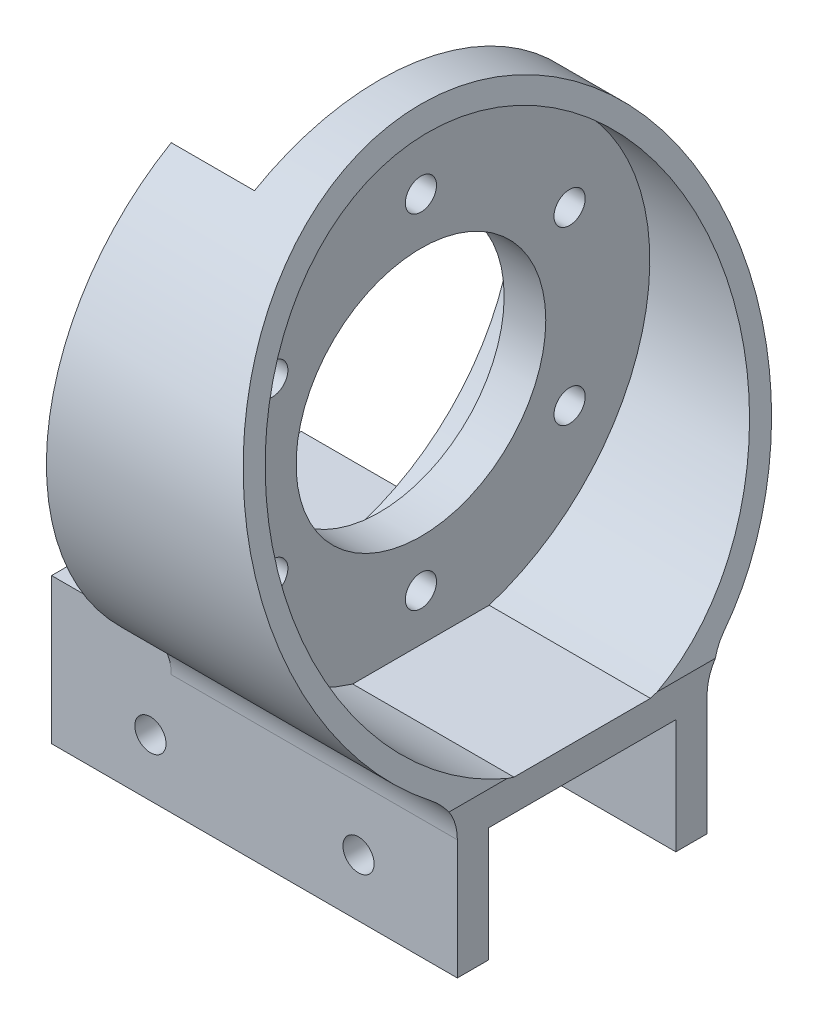
SolidWorks part; units mm, degrees
material "6061 合金"
ref_plane "前视基准面" through (0, 0, 0) normal (0, 0, 1) x (1, 0, 0)
ref_plane "上视基准面" through (0, 0, 0) normal (0, 1, 0) x (1, 0, 0)
ref_plane "右视基准面" through (0, 0, 0) normal (1, 0, 0) x (0, 0, -1)
sketch "草图1" plane through (0, 0, 0) normal (0, 0, 1) x (1, 0, 0)
  line L1 (-17, -14.5) -> (17, -14.5)
  line L2 (-17, -14.5) -> (-17, 14.5)
  line L3 (-17, 14.5) -> (17, 14.5)
  line L4 (17, -14.5) -> (17, 14.5)
  line L5 (-17, -14.5) -> (17, 14.5) construction
  line L6 (-17, 14.5) -> (17, -14.5) construction
  point P0 (0, 0)
  dimension "D1" = 34
  dimension "D2" = 29
extrude "凸台-拉伸1" add sketch "草图1" along normal blind 20
sketch "草图2" plane through (0, 0, 20) normal (0, 0, 1) x (1, 0, 0)
  line L9 (-12, 9.5) -> (-12, 16.0588)
  line L10 (-12, 16.0588) -> (12, 16.0588)
  line L11 (12, 16.0588) -> (12, 9.5)
  line L13 (12, -9.5) -> (12, 9.5)
  line L14 (12, 9.5) -> (-12, 9.5)
  line L15 (-12, 9.5) -> (-12, -9.5)
  line L16 (-12, -9.5) -> (12, -9.5)
  line L17 (12, -9.5) -> (12, 9.5)
  line L19 (-12, 9.5) -> (-12, -9.5)
  line L20 (-12, -9.5) -> (12, -9.5)
  dimension "D1" = 5
extrude "切除-拉伸1" cut sketch "草图2" against normal through all
sketch "草图3" plane through (17, 0, 0) normal (1, 0, 0) x (0, 0, -1)
  line L0 (-20, 14.5) -> (0, 14.5) construction
  circle A0 centre (-10, 2.5) radius 2.75
  dimension "D1" = 5.5
  dimension "D2" = 12
extrude "切除-拉伸2" cut sketch "草图3" against normal through all
sketch "草图4" plane through (17, 0, 0) normal (1, 0, 0) x (0, 0, -1)
  line L0 (-10, 2.5) -> (-10, 14.5) construction
  line L1 (-20, 14.5) -> (0, 14.5) construction
  line L2 (-10, 2.5) -> (-15.8839, 12.6912) construction
  circle A0 centre (-10, 2.5) radius 7 construction
  circle A1 centre (-13.5, 8.5622) radius 1.65
  circle A2 centre (-3.9378, 6) radius 1.65
  circle A3 centre (-6.5, -3.5622) radius 1.65
  circle A4 centre (-16.0622, -1) radius 1.65
  point P18 (-10, 2.5)
  dimension "D1" = 30
  dimension "D2" = 4
extrude "切除-拉伸3" cut sketch "草图4" against normal blind 20
sketch "草图5" plane through (17, 0, 0) normal (1, 0, 0) x (0, 0, -1)
  line L0 (-25, -9.5) -> (5, -9.5)
  line L1 (-20, -14.5) -> (0, -14.5) construction
  line L2 (-20, -14.5) -> (-20, 14.5) construction
  line L3 (0, -14.5) -> (0, 14.5) construction
  line L4 (-25, -9.5) -> (-25, -34.5)
  line L5 (-25, -34.5) -> (-20, -34.5)
  line L6 (-20, -34.5) -> (-20, -14.5)
  line L7 (-20, -14.5) -> (0, -14.5)
  line L8 (0, -14.5) -> (0, -34.5)
  line L9 (0, -34.5) -> (5, -34.5)
  line L10 (5, -34.5) -> (5, -9.5)
  dimension "D1" = 5
  dimension "D2" = 5
  dimension "D3" = 5
extrude "凸台-拉伸2" add sketch "草图5" along normal blind 15 and the other way blind 40
sketch "草图6" plane through (32, 0, 0) normal (1, 0, 0) x (0, 0, -1)
  line L6 (-20.7, -34.5) -> (0.7, -34.5)
  line L9 (0.7, -13.8) -> (0.7, -34.5)
  line L10 (-20.7, -13.8) -> (0.7, -13.8)
  line L11 (-20.7, -34.5) -> (-20.7, -13.8)
  line L12 (0.7, -13.8) -> (0.7, -34.5)
  line L13 (-20.7, -13.8) -> (0.7, -13.8)
  line L14 (-20.7, -34.5) -> (-20.7, -13.8)
  dimension "D1" = 0.7
extrude "切除-拉伸4" cut sketch "草图6" against normal through all
sketch "草图8" plane through (17, 0, 0) normal (1, 0, 0) x (0, 0, -1)
  line L0 (-20, 14.5) -> (-20, -9.5)
  line L1 (-20, 14.5) -> (-25, -9.5)
  line L2 (-25, -9.5) -> (-20, -9.5)
  line L3 (0, 14.5) -> (0, -9.5)
  line L4 (0, -9.5) -> (5, -9.5)
  line L5 (5, -9.5) -> (0, 14.5)
extrude "凸台-拉伸3" add sketch "草图8" against normal up to surface (5 mm away) up to face at (12, -1, 14.4122)
sketch "草图9" plane through (-17, 0, 0) normal (-1, 0, 0) x (0, 0, 1)
  line L0 (0, 14.5) -> (-5, -9.5)
  line L1 (-5, -9.5) -> (0, -9.5)
  line L2 (0, -9.5) -> (0, 14.5)
  line L3 (20, 14.5) -> (20, -9.5)
  line L4 (20, -9.5) -> (25, -9.5)
  line L5 (25, -9.5) -> (20, 14.5)
extrude "凸台-拉伸4" add sketch "草图9" against normal up to surface (5 mm away) up to face at (-12, 2.5, 12.75)
fillet "圆角1" radius 10 4 edges at (14.5, 14.5, 0) (14.5, 14.5, 20) (-14.5, 14.5, 20) (-14.5, 14.5, 0)
sketch "草图11" plane through (32, 0, 0) normal (1, 0, 0) x (0, 0, -1)
  line L0 (-10, -13.8) -> (-10, -34.5) construction
  line L1 (0.7, -13.8) -> (-20.7, -13.8) construction
  circle A0 centre (-10, -24.15) radius 12
  dimension "D1" = 24
extrude "切除-拉伸6" cut sketch "草图11" against normal blind 56
sketch "草图12" plane through (32, 0, 0) normal (1, 0, 0) x (0, 0, -1)
  line L0 (-10, -24.15) -> (-10, -12.15) construction
  line L1 (-10, -24.15) -> (8.0772, -13.7131)
  line L2 (-10, -24.15) -> (-28.0772, -13.7131)
  line L3 (-28.0772, -13.7131) -> (-28.0772, -37.2815)
  line L4 (-28.0772, -37.2815) -> (9.633, -37.2815)
  line L5 (9.633, -37.2815) -> (8.0772, -13.7131)
  arc A0 (-3.9273, -13.8) -> (-16.0727, -13.8) centre (-10, -24.15) ccw construction
  dimension "D1" = 60
extrude "切除-拉伸7" cut sketch "草图12" against normal blind 56
sketch "草图13" plane through (32, 0, 0) normal (1, 0, 0) x (0, 0, -1)
  line L0 (5, -15.4897) -> (0.7, -17.9724) construction
  line L1 (-20.7, -17.9724) -> (-25, -15.4897) construction
  line L2 (5, -15.4897) -> (0.3923, -18.15)
  line L3 (-20.3923, -18.15) -> (-25, -15.4897)
  line L4 (5, -9.5) -> (-25, -9.5) construction
  line L5 (-0.76, -9.5) -> (-19.24, -9.5)
  arc A0 (0.3923, -18.15) -> (-20.3923, -18.15) centre (-10, -24.15) ccw
  arc A1 (5, -15.4897) -> (-0.76, -9.5) centre (-10, -24.15) ccw
  arc A2 (-19.24, -9.5) -> (-25, -15.4897) centre (-10, -24.15) ccw
extrude "凸台-拉伸5" add sketch "草图13" against normal up to surface (55 mm away) up to face at (-23, -13.9474, 10)
sketch "草图14" plane through (32, 0, 0) normal (1, 0, 0) x (0, 0, -1)
  line L0 (-10, -12.15) -> (-10, -6.8295) construction
  line L1 (1.5911, -21.0442) -> (6.7303, -19.6671)
  line L2 (-21.5911, -21.0442) -> (-26.7303, -19.6671)
  line L3 (5, -9.5) -> (-25, -9.5) construction
  line L4 (-0.76, -9.5) -> (-19.24, -9.5)
  arc A0 (1.5911, -21.0442) -> (-21.5911, -21.0442) centre (-10, -24.15) ccw
  arc A1 (6.7303, -19.6671) -> (-0.76, -9.5) centre (-10, -24.15) ccw
  arc A2 (-19.24, -9.5) -> (-26.7303, -19.6671) centre (-10, -24.15) ccw
  dimension "D1" = 75
extrude "凸台-拉伸6" add sketch "草图14" against normal up to surface (55 mm away) contours L4 A2 L2 A0 L1 A1 up to face at (-23, -13.3799, 10)
sketch "草图15" plane through (32, 0, 0) normal (1, 0, 0) x (0, 0, -1)
  line L0 (-10, -12.15) -> (-10, -24.65) construction
  arc A0 (1.5911, -21.0442) -> (-21.5911, -21.0442) centre (-10, -24.15) ccw construction
  circle A1 centre (-10, -24.65) radius 12.5
  dimension "D1" = 12.5
extrude "切除-拉伸8" cut sketch "草图15" against normal blind 180
sketch "草图17" plane through (32, 0, 0) normal (1, 0, 0) x (0, 0, -1)
  line L0 (-10, -24.65) -> (-10, -12.15) construction
  line L1 (-10, -24.65) -> (5.8905, -15.4756) construction
  line L2 (-10, -24.65) -> (-25.8905, -15.4756) construction
  line L3 (-20.8253, -18.4) -> (-14.9708, -8.2597) construction
  line L4 (0.8253, -18.4) -> (-5.6497, -7.1849) construction
  arc A0 (1.9401, -20.9507) -> (-21.9401, -20.9507) centre (-10, -24.65) ccw construction
  dimension "D1" = 60
sketch "草图18" plane through (32, 0, 0) normal (1, 0, 0) x (0, 0, -1)
  line L0 (-10, -24.65) -> (-10, -24.5) construction
  circle A1 centre (-10, -24.5) radius 12.5
  dimension "D1" = 0.15
  dimension "D2" = 25
extrude "切除-拉伸9" cut sketch "草图18" against normal blind 58
sketch "草图21" plane through (-23, 0, 0) normal (-1, 0, 0) x (0, 0, 1)
  line L1 (-17.6613, 18.996) -> (42.1159, 18.996)
  line L2 (-17.6613, 18.996) -> (-17.6613, -31.8849)
  line L3 (-17.6613, -31.8849) -> (42.1159, -31.8849)
  line L4 (42.1159, 18.996) -> (42.1159, -31.8849)
extrude "切除-拉伸10" cut sketch "草图21" against normal blind 16
sketch "草图22" plane through (17, 0, 0) normal (1, 0, 0) x (0, 0, -1)
  line L1 (-25, -9.5) -> (5, -9.5)
  line L2 (-25, -9.5) -> (-25, 14.5)
  line L3 (-25, 14.5) -> (5, 14.5)
  line L4 (5, -9.5) -> (5, 14.5)
  circle A0 centre (-6.5, -3.5622) radius 1.65 construction
  circle A1 centre (-3.9378, 6) radius 1.65 construction
  circle A2 centre (-13.5, 8.5622) radius 1.65 construction
  circle A3 centre (-10, 2.5) radius 2.75 construction
  circle A4 centre (-16.0622, -1) radius 1.65 construction
  circle A5 centre (-6.5, -3.5622) radius 1.65
  circle A6 centre (-3.9378, 6) radius 1.65
  circle A7 centre (-13.5, 8.5622) radius 1.65
  circle A8 centre (-10, 2.5) radius 2.75
  circle A9 centre (-16.0622, -1) radius 1.65
  dimension "D1" = 24
  dimension "D2" = 30
extrude "凸台-拉伸7" add sketch "草图22" against normal up to surface (5 mm away) up to face at (12, -1, 14.4122)
sketch "草图23" plane through (17, 0, 0) normal (1, 0, 0) x (0, 0, -1)
  line L4 (-25, 14.5) -> (-25, -9.5)
  line L5 (-25, -9.5) -> (5, -9.5)
  line L6 (5, -9.5) -> (5, 14.5)
  line L7 (5, 14.5) -> (-25, 14.5)
  line L8 (-25, 14.5) -> (-25, -9.5)
  line L9 (-25, -9.5) -> (5, -9.5)
  line L10 (5, -9.5) -> (5, 14.5)
  line L11 (5, 14.5) -> (-25, 14.5)
  dimension "D1" = 0
extrude "切除-拉伸11" cut sketch "草图23" against normal blind 1
sketch "草图24" plane through (16, 0, 0) normal (1, 0, 0) x (0, 0, -1)
  line L1 (-25, 14.5) -> (-23, 14.5)
  line L2 (-25, 14.5) -> (-25, -9.5)
  line L3 (-25, -9.5) -> (-23, -9.5)
  line L4 (-23, 14.5) -> (-23, -9.5)
  line L5 (-25, -9.5) -> (5, -9.5) construction
  line L7 (5, 14.5) -> (3, 14.5)
  line L8 (5, 14.5) -> (5, -9.5)
  line L9 (5, -9.5) -> (3, -9.5)
  line L10 (3, 14.5) -> (3, -9.5)
  circle A0 centre (-10, 2.5) radius 10.5 construction
  dimension "D1" = 21
  dimension "D2" = 24
  dimension "D3" = 2
  dimension "D4" = 24
  dimension "D5" = 2
extrude "凸台-拉伸8" add sketch "草图24" along normal up to surface (16 mm away) up to face at (32, -15.2675, 10)
sketch "草图25" plane through (0, 0, -3) normal (0, 0, 1) x (1, 0, 0)
  line L0 (16, 14.5) -> (32, -9.5)
  line L1 (32, -9.5) -> (32, 14.5)
  line L2 (32, 14.5) -> (16, 14.5)
extrude "切除-拉伸12" cut sketch "草图25" against normal mid plane 62
sketch "草图26" plane through (32, 0, 0) normal (1, 0, 0) x (0, 0, -1)
  line L0 (5, -15.4897) -> (5, -25.9673)
  line L1 (5, -25.9673) -> (8.7839, -25.4832)
  line L2 (8.7839, -25.4832) -> (7.5054, -15.4897)
  line L3 (7.5054, -15.4897) -> (5, -15.4897)
  line L4 (-25, -15.4897) -> (-25, -25.9673)
  line L5 (-25, -25.9673) -> (-32.0692, -23.4308)
  line L6 (-32.0692, -23.4308) -> (-32.0692, -17.5217)
  line L7 (-32.0692, -17.5217) -> (-25, -15.4897)
extrude "切除-拉伸13" cut sketch "草图26" against normal blind 62
sketch "草图28" plane through (32, 0, 0) normal (1, 0, 0) x (0, 0, -1)
  line L0 (1.9822, -20.9394) -> (5, -20.9394)
  line L1 (5, -20.9394) -> (5, -20.1308)
  line L2 (5, -20.1308) -> (1.9822, -20.9394)
  line L3 (-21.9822, -20.9394) -> (-25, -20.9394)
  line L4 (-25, -20.9394) -> (-25, -20.1308)
  line M1 (1.9822, -20.9394) -> (5, -20.1308)
  line M7 (-25, -20.1308) -> (-21.9822, -20.9394)
extrude "凸台-拉伸9" add sketch "草图28" along direction (-1, 0, 0) on the side against the normal up to surface (39 mm away) contours L0 L1 M1 | L4 L3 M7 region at (32, -20.6698, -3.9941) region at (32, -20.6698, 23.9941) up to face at (-7, -15.3668, 10)
sketch "草图30" plane through (12, 0, 0) normal (-1, 0, 0) x (0, 0, 1)
  arc A2 (-0.4941, 2.1468) -> (-2.4952, 9.1423) centre (-15.4856, 1.6423) ccw
  arc A3 (-0.4941, 2.1468) -> (15.5529, 11.4115) centre (10, 2.5) ccw
  arc A5 (10.4952, 16.6423) -> (15.5529, 11.4115) centre (23.4856, 24.1423) ccw
sketch "草图32" plane through (-7, 0, 0) normal (-1, 0, 0) x (0, 0, 1)
  line L0 (10, -12) -> (10, -24.5) construction
  line L1 (10, -24.5) -> (25.0466, -15.8128) construction
  line L2 (20.8253, -18.25) -> (16.0889, -10.0462) construction
  arc A0 (21.9822, -20.9394) -> (-1.9822, -20.9394) centre (10, -24.5) ccw construction
  dimension "D1" = 60
ref_plane "基准面1" through (0, 4.4551, 7.7165) normal (0, 0.5, 0.866) x (0, 0.866, -0.5)
ref_plane "基准面2" through (0, 0, 10) normal (0, 0, -1) x (-1, 0, 0)
fillet "圆角3" radius 4 2 edges at (24, -9.5, 23) (24, -9.5, -3)
sketch "草图35" plane through (12, 0, 0) normal (-1, 0, 0) x (0, 0, 1)
  line L3 (25, 13.4808) -> (22.4952, 9.1423)
  line L4 (25, -9.5) -> (25, 14.5) construction
  line L5 (-5, -9.5) -> (25, -9.5) construction
  line L6 (-5, 14.5) -> (-5, -9.5) construction
  line L7 (-5, 14.5) -> (25, 14.5) construction
  line L8 (25, -9.5) -> (25, 13.4808)
  line L9 (-5, -9.5) -> (25, -9.5)
  line L10 (-5, 14.5) -> (-5, -9.5)
  line L11 (-5, 14.5) -> (8.0047, 14.5)
  arc A3 (4.4471, 11.4115) -> (8.0047, 14.5) centre (-3.4856, 24.1423) ccw
  arc A4 (22.4952, 9.1423) -> (20.4941, 2.1468) centre (35.4856, 1.6423) ccw
  arc A5 (4.4471, 11.4115) -> (20.4941, 2.1468) centre (10, 2.5) ccw
extrude "凸台-拉伸10" add sketch "草图35" along normal blind 8
sketch "草图36" plane through (12, 0, 0) normal (-1, 0, 0) x (0, 0, 1)
  line L1 (25, -9.5) -> (-5, -9.5)
  line L2 (25, -9.5) -> (25, 14.5)
  line L3 (25, 14.5) -> (-5, 14.5)
  line L4 (-5, -9.5) -> (-5, 14.5)
extrude "切除-拉伸15" cut sketch "草图36" along normal blind 13
sketch "草图37" plane through (16, 0, 0) normal (1, 0, 0) x (0, 0, -1)
  circle A0 centre (-10, 2.5) radius 11.5
  dimension "D1" = 23
extrude "切除-拉伸16" cut sketch "草图37" against normal blind 13
sketch "草图38" plane through (12, 0, 0) normal (-1, 0, 0) x (0, 0, 1)
  line L4 (-5, -9.5) -> (25, -9.5)
  line L5 (25, -9.5) -> (25, 14.5)
  line L6 (25, 14.5) -> (-5, 14.5)
  line L7 (-5, 14.5) -> (-5, -9.5)
  line L8 (-5, -9.5) -> (25, -9.5)
  line L9 (25, -9.5) -> (25, 14.5)
  line L10 (25, 14.5) -> (-5, 14.5)
  line L11 (-5, 14.5) -> (-5, -9.5)
  dimension "D1" = 0
extrude "切除-拉伸17" cut sketch "草图38" against normal blind 28
ref_plane "基准面3" through (12.5, 0, 0) normal (1, 0, 0) x (0, 0, -1)
sketch "草图39" plane through (12.5, 0, 0) normal (1, 0, 0) x (0, 0, -1)
  line L0 (-10, -9.5) -> (-10, 11.5) construction
  line L1 (5, -9.5) -> (-25, -9.5) construction
  circle A0 centre (-10, 11.5) radius 12
  circle A1 centre (-10, 11.5) radius 21
  circle A2 centre (-10, 11.5) radius 16.5 construction
  circle A3 centre (-10, 28) radius 1.5
  circle A4 centre (4.2894, 19.75) radius 1.5
  circle A5 centre (4.2894, 3.25) radius 1.5
  circle A6 centre (-10, -5) radius 1.5
  circle A7 centre (-24.2894, 3.25) radius 1.5
  circle A8 centre (-24.2894, 19.75) radius 1.5
  point P25 (-10, 11.5)
  dimension "D2" = 24
  dimension "D3" = 42
  dimension "D4" = 33
  dimension "D5" = 3
  dimension "D1" = 21
  dimension "D6" = 6
extrude "凸台-拉伸11" add sketch "草图39" along normal blind 4 separate body
sketch "草图42" plane through (16.5, 0, 0) normal (1, 0, 0) x (0, 0, -1)
  line L0 (5, -9.5) -> (5, -3.1969)
  line L1 (5, -3.1969) -> (-10, -7.4384)
  line L2 (-10, -7.4384) -> (-25, -3.1969)
  line L3 (-25, -3.1969) -> (-25, -9.5)
  line L4 (5, -9.5) -> (-25, -9.5) construction
  line L5 (-25, -9.5) -> (5, -9.5)
  circle A0 centre (-10, 11.5) radius 21 construction
extrude "凸台-拉伸14" add sketch "草图42" against normal blind 4
fillet "圆角5" radius 10 2 edges at (14.5, -3.1969, -5) (14.5, -3.1969, 25)
sketch "草图43" plane through (12.5, 0, 0) normal (-1, 0, 0) x (0, 0, 1)
  line L3 (25, -9.5) -> (-5, -9.5) construction
  line L4 (21.619, -9.5) -> (-1.619, -9.5)
  line L5 (25, -6.8303) -> (25, -9.5) construction
  line L6 (-5, -9.5) -> (-5, -6.8303) construction
  line L7 (25, -7.235) -> (25, -9.5)
  line L8 (-5, -9.5) -> (-5, -7.235)
  line L9 (25, -9.5) -> (-5, -9.5)
  line L10 (-2, 11.5) -> (-14, 11.5)
  line L11 (16, 21.8923) -> (22, 32.2846)
  line L12 (10, 11.5) -> (10, 32.5)
  arc A0 (26.9355, -0.9173) -> (-6.9355, -0.9173) centre (10, 11.5) ccw construction
  arc A3 (-14, 11.5) -> (-5, -7.235) centre (10, 11.5) ccw
  arc A4 (-11, 11.5) -> (20.5, 29.6865) centre (10, 11.5) ccw
  arc A5 (25, -7.235) -> (22, 32.2846) centre (10, 11.5) ccw
  circle A6 centre (10, 11.5) radius 12 construction
  arc A7 (-2, 11.5) -> (16, 21.8923) centre (10, 11.5) ccw
  line M1 (25, -9.5) -> (25, -6.8303)
  arc M2 (25, -6.8303) -> (26.9355, -0.9173) centre (35, -6.8303) cw
  arc M3 (26.9355, -0.9173) -> (-6.9355, -0.9173) centre (10, 11.5) ccw
  arc M4 (-6.9355, -0.9173) -> (-5, -6.8303) centre (-15, -6.8303) cw
  line M5 (-5, -6.8303) -> (-5, -9.5)
  line M6 (-5, -9.5) -> (25, -9.5)
  dimension "D1" = 48
  dimension "D2" = 30
extrude "凸台-拉伸15" add sketch "草图43" against normal blind 4 contours A4 M4 M5 M6 | A4 L9 M6 M1 M2 | A5 M1 M3 M2 | A3 M5 M4 M3 region at (12.5, -7.4887, 21.5485) region at (12.5, -7.4887, -1.5485) region at (12.5, 2.6841, -10.0948) region at (12.5, 15.9074, 30.9592)
extrude "凸台-拉伸16" add sketch "草图43<4>" along normal blind 8 contours A4 L9 M6 M1 M2 | A4 M4 M5 M6 | A3 M5 M4 M3 | A5 M1 M3 M2 region at (12.5, -7.4887, 21.5485) region at (12.5, -7.4887, -1.5485) region at (12.5, 2.6841, -10.0948) region at (12.5, 15.9074, 30.9592)
sketch "草图43<4>" plane through (12.5, 0, 0) normal (-1, 0, 0) x (0, 0, 1) same geometry as "草图43"
sketch "草图45" plane through (12.5, 0, 0) normal (-1, 0, 0) x (0, 0, 1)
  line L0 (-11, 11.5) -> (-14, 11.5) construction
  line L1 (20.5, 29.6865) -> (22, 32.2846) construction
  line L2 (-11, 11.5) -> (-14, 11.5)
  line L3 (20.5, 29.6865) -> (22, 32.2846)
  arc A0 (22, 32.2846) -> (-14, 11.5) centre (10, 11.5) ccw
  arc A1 (20.5, 29.6865) -> (-11, 11.5) centre (10, 11.5) ccw
extrude "凸台-拉伸18" add sketch "草图45" against normal up to surface (4 mm away) up to face at (16.5, 7.5452, 7.5685)
sketch "草图49" plane through (-7, 0, 0) normal (-1, 0, 0) x (0, 0, 1)
  line L0 (10, -9.5) -> (10, -12.5) construction
  line L1 (25, -9.5) -> (-5, -9.5) construction
  line L2 (10, -12.5) -> (22.5, -12.5) construction
  line L4 (22.5, -12.5) -> (-2.5, -12.5)
  line L5 (22.5, -12.5) -> (22.5, -37.5)
  line L6 (22.5, -37.5) -> (-2.5, -37.5)
  line L7 (-2.5, -12.5) -> (-2.5, -37.5)
  dimension "D1" = 3
  dimension "D2" = 12.5
  dimension "D3" = 25
extrude "切除-拉伸20" cut sketch "草图49" against normal blind 45
sketch "草图50" plane through (-7, 0, 0) normal (-1, 0, 0) x (0, 0, 1)
  line L0 (6.5, -12.5) -> (13.5, -12.5)
  arc A0 (13.5, -12.5) -> (6.5, -12.5) centre (10, -24.5) ccw construction
  arc A1 (13.5, -12.5) -> (6.5, -12.5) centre (10, -24.5) ccw
extrude "凸台-拉伸20" add sketch "草图50" against normal up to surface (39 mm away) up to face at (32, -15.2258, 10)
sketch "草图51" plane through (0, -20.9394, 0) normal (0, -1, 0) x (1, 0, 0)
  line L4 (-7, 25) -> (-7, 22.5)
  line L5 (-7, 22.5) -> (32, 22.5)
  line L6 (32, 22.5) -> (32, 25)
  line L7 (32, 25) -> (-7, 25)
  line L8 (-7, 25) -> (-7, 22.5)
  line L9 (-7, 22.5) -> (32, 22.5)
  line L10 (32, 22.5) -> (32, 25)
  line L11 (32, 25) -> (-7, 25)
  line L12 (32, -2.5) -> (-7, -2.5)
  line L13 (-7, -2.5) -> (-7, -5)
  line L14 (-7, -5) -> (32, -5)
  line L15 (32, -5) -> (32, -2.5)
  line L16 (32, -2.5) -> (-7, -2.5)
  line L17 (-7, -2.5) -> (-7, -5)
  line L18 (-7, -5) -> (32, -5)
  line L19 (32, -5) -> (32, -2.5)
  dimension "D1" = 0
  dimension "D2" = 0
extrude "凸台-拉伸21" add sketch "草图51" along normal blind 11.56
sketch "草图52" plane through (0, 0, 25) normal (0, 0, 1) x (1, 0, 0)
  line L0 (-7, -32.4994) -> (-7, -22.4994) construction
  line L1 (-7, -9.5) -> (-7, -32.4994) construction
  line L2 (-7, -22.4994) -> (32, -22.4994) construction
  line L3 (32, -9.5) -> (32, -32.4994) construction
  line L5 (-2.5, -28.4994) -> (27.5, -28.4994) construction
  line L6 (-2.5, -28.4994) -> (-2.5, -16.4994) construction
  line L7 (-2.5, -16.4994) -> (27.5, -16.4994) construction
  line L8 (27.5, -28.4994) -> (27.5, -16.4994) construction
  line L9 (-2.5, -28.4994) -> (27.5, -16.4994) construction
  line L10 (-2.5, -16.4994) -> (27.5, -28.4994) construction
  circle A0 centre (-2.5, -16.4994) radius 1.5
  circle A1 centre (-2.5, -28.4994) radius 1.5
  circle A2 centre (27.5, -16.4994) radius 1.5
  circle A3 centre (27.5, -28.4994) radius 1.5
  point P8 (12.5, -22.4994)
  dimension "D4" = 3
  dimension "D5" = 3
  dimension "D6" = 3
  dimension "D7" = 3
  dimension "D1" = 10
  dimension "D2" = 12
  dimension "D3" = 30
extrude "切除-拉伸21" cut sketch "草图52" against normal blind 44.56
sketch "草图55" plane through (-7, 0, 0) normal (-1, 0, 0) x (0, 0, 1)
  circle A0 centre (10, 11.5) radius 24
  circle A1 centre (10, 11.5) radius 54.9756
extrude "切除-拉伸29" cut sketch "草图55" against normal blind 58
sketch "草图56" plane through (-7, 0, 0) normal (-1, 0, 0) x (0, 0, 1)
  line L0 (10, -9.5) -> (10, -12.5) construction
  line L1 (21.619, -9.5) -> (-1.619, -9.5) construction
  line L2 (10, -12.5) -> (10, -24.5) construction
  line L3 (1, -37.5) -> (-2, -37.5)
  line L5 (-2, -37.5) -> (-2, -9.5)
  line L6 (-2, -9.5) -> (22, -9.5)
  line L7 (22, -37.5) -> (22, -9.5)
  line L8 (-0.4, -37.5) -> (1, -35.75) construction
  line L9 (10, -12.5) -> (19, -12.5)
  line L11 (1, -37.5) -> (1, -12.5)
  line L13 (19, -37.5) -> (19, -12.5)
  line L14 (10, -12.5) -> (1, -12.5)
  line L16 (19, -37.5) -> (22, -37.5)
  line L17 (19, -35.75) -> (20.4, -37.5) construction
  dimension "D1" = 3
  dimension "D2" = 12
  dimension "D6" = 18
extrude "凸台-拉伸22" add sketch "草图56" against normal up to surface (39 mm away) up to face at (32, -11, 10)
sketch "草图57" plane through (0, -9.5, 0) normal (0, 1, 0) x (1, 0, 0)
  line L8 (4.5, 1.619) -> (16.5, 1.619) construction
  line L9 (16.5, -21.619) -> (4.5, -21.619) construction
  line L10 (4.5, 1.619) -> (16.5, 1.619)
  line L11 (16.5, -21.619) -> (4.5, -21.619)
  line L12 (4.5, 1.619) -> (4.5, 2)
  line L13 (4.5, 11) -> (4.5, -10) construction
  line L14 (32, 2) -> (-7, 2) construction
  line L15 (4.5, 2) -> (16.5, 2)
  line L16 (16.5, 2) -> (16.5, 1.619)
  line L17 (4.5, -21.619) -> (4.5, -22)
  line L18 (32, -22) -> (-7, -22) construction
  line L19 (4.5, -22) -> (16.5, -22)
  line L20 (16.5, -34) -> (16.5, 14) construction
  line L21 (16.5, -22) -> (16.5, -21.619)
extrude "凸台-拉伸23" add sketch "草图57" along normal blind 1
sketch "草图59" plane through (0, 0, -2) normal (0, 0, -1) x (-1, 0, 0)
  line L1 (-32, -37.5) -> (7, -37.5)
  line L2 (-32, -37.5) -> (-32, -23.5)
  line L3 (-32, -23.5) -> (7, -23.5)
  line L4 (7, -37.5) -> (7, -23.5)
  line L5 (7, -9.5) -> (7, -37.5) construction
  dimension "D1" = 14
  dimension "D2" = 39
extrude "切除-拉伸31" cut sketch "草图59" against normal blind 35
sketch "草图61" plane through (16.5, 0, 0) normal (1, 0, 0) x (0, 0, -1)
  circle A0 centre (-10, 11.5) radius 24
  circle A1 centre (-10, 11.5) radius 22
  dimension "D1" = 44
extrude "凸台-拉伸24" add sketch "草图61" along normal up to surface (15.5 mm away) up to face at (32, -17.25, 10)
sketch "草图62" plane through (0, -9.5, 0) normal (0, 1, 0) x (1, 0, 0)
  line L4 (32, -21.619) -> (16.5, -21.619)
  line L5 (16.5, -21.619) -> (16.5, -22)
  line L6 (16.5, -22) -> (32, -22)
  line L7 (32, -22) -> (32, -21.619)
  line L8 (32, -21.619) -> (16.5, -21.619)
  line L9 (16.5, -21.619) -> (16.5, -22)
  line L10 (16.5, -22) -> (32, -22)
  line L11 (32, -22) -> (32, -21.619)
  line L12 (16.5, 1.619) -> (32, 1.619)
  line L13 (32, 1.619) -> (32, 2)
  line L14 (32, 2) -> (16.5, 2)
  line L15 (16.5, 2) -> (16.5, 1.619)
  line L16 (16.5, 1.619) -> (32, 1.619)
  line L17 (32, 1.619) -> (32, 2)
  line L18 (32, 2) -> (16.5, 2)
  line L19 (16.5, 2) -> (16.5, 1.619)
  dimension "D1" = 0
  dimension "D2" = 0
extrude "凸台-拉伸25" add sketch "草图62" along normal blind 1
sketch "草图63" plane through (0, 0, 22) normal (0, 0, 1) x (1, 0, 0)
  line L0 (32, -9.2846) -> (16.5, -9.2846) construction
  line L1 (4.5, -9.2846) -> (32, -9.2846) construction
  line L2 (32, -9.2846) -> (32, 35.5)
  line L3 (32, 35.5) -> (16.5, 35.5)
  line L4 (32, 35.5) -> (12.5, 35.5) construction
  line L5 (16.5, 35.5) -> (32, -9.2846)
  dimension "D1" = 15.5
extrude "切除-拉伸32" cut sketch "草图63" against normal mid plane 148
fillet "圆角7" radius 5 2 edges at (18.25, -9.2846, 22) (18.25, -9.2846, -2)
sketch "草图64" plane through (-7, 0, 0) normal (-1, 0, 0) x (0, 0, 1)
  line L0 (10, -9.5) -> (22.6668, -9.5) construction
  line L2 (-2, -11.9947) -> (-2, -9.5)
  line L4 (22, -11.9947) -> (22, -9.5)
  line L5 (-2, -9.5) -> (-2.6668, -9.5)
  line L13 (19, -23.5) -> (22, -23.5)
  line L14 (22, -23.5) -> (22, -11.9947)
  line L15 (22.6668, -9.5) -> (-2.6668, -9.5)
  line L16 (-2, -11.9947) -> (-2, -23.5)
  line L17 (-2, -23.5) -> (1, -23.5)
  line L18 (1, -23.5) -> (1, -12.5)
  line L19 (1, -12.5) -> (19, -12.5)
  line L20 (19, -12.5) -> (19, -23.5)
  line L23 (22.6668, -9.5) -> (22, -9.5)
  arc A2 (22.6668, -9.5) -> (22, -11.9947) centre (27, -11.9947) ccw
  arc A3 (-2, -11.9947) -> (-2.6668, -9.5) centre (-7, -11.9947) ccw
  arc A4 (22.6668, -9.5) -> (22, -11.9947) centre (27, -11.9947) ccw
  arc A5 (-2, -11.9947) -> (-2.6668, -9.5) centre (-7, -11.9947) ccw
  dimension "D1" = 0
extrude "切除-拉伸33" cut sketch "草图64" against normal up to surface (11.5 mm away) up to face at (4.5, 6.3271, 25.0243)
sketch "草图65" plane through (0, 0, -2) normal (0, 0, -1) x (-1, 0, 0)
  line L0 (-12.5, -23.5) -> (-12.5, -18) construction
  line L1 (7, -23.5) -> (-32, -23.5) construction
  line L2 (-12.5, 7.8185) -> (-12.5, -7.8185) construction
  line L3 (-12.5, -18) -> (-2.5, -18) construction
  line L4 (-2.5, -18) -> (-22.5, -18) construction
  circle A0 centre (-22.5, -18) radius 1.5
  circle A1 centre (-2.5, -18) radius 1.5
  dimension "D4" = 3
  dimension "D5" = 3
  dimension "D1" = 5.5
  dimension "D2" = 10
  dimension "D3" = 20
extrude "切除-拉伸34" cut sketch "草图65" against normal blind 148
